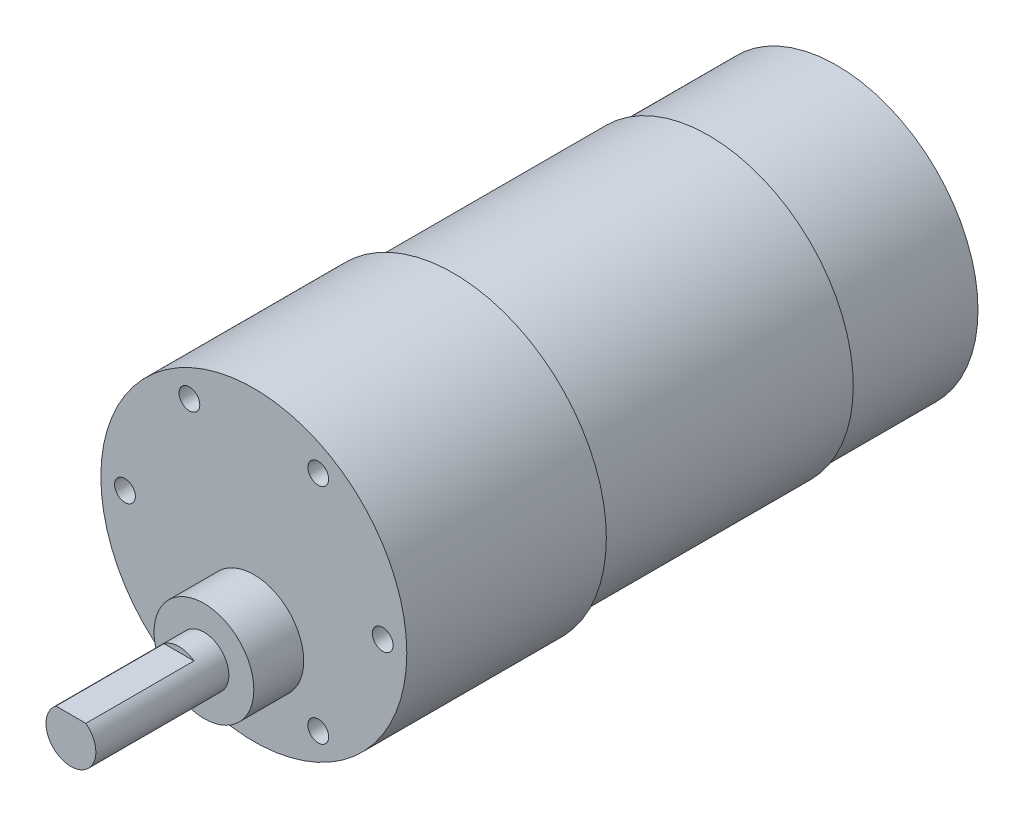
SolidWorks part; units mm, degrees
ref_plane "Front Plane" through (0, 0, 0) normal (0, 0, 1) x (1, 0, 0)
ref_plane "Top Plane" through (0, 0, 0) normal (0, 1, 0) x (1, 0, 0)
ref_plane "Right Plane" through (0, 0, 0) normal (1, 0, 0) x (0, 0, -1)
sketch "Sketch1" plane through (0, 0, 0) normal (0, 0, 1) x (1, 0, 0)
  circle A0 centre (0, 0) radius 18.4
  dimension "D1" = 36.8
extrude "Boss-Extrude1" add sketch "Sketch1" against normal blind 24
sketch "Sketch2" plane through (0, 0, -24) normal (0, 0, -1) x (-1, 0, 0)
  circle A0 centre (0, 0) radius 17.4
  dimension "D1" = 34.8
extrude "Boss-Extrude2" add sketch "Sketch2" along normal blind 30.7
sketch "Sketch3" plane through (0, 0, -54.7) normal (0, 0, -1) x (-1, 0, 0)
  circle A0 centre (0, 0) radius 17
  dimension "D1" = 34
extrude "Boss-Extrude3" add sketch "Sketch3" along normal blind 15.4
sketch "Sketch4" plane through (0, 0, 0) normal (0, 0, 1) x (1, 0, 0)
  circle A0 centre (0, -7) radius 6
  dimension "D1" = 12
  dimension "D2" = 7
extrude "Boss-Extrude4" add sketch "Sketch4" along normal blind 6
sketch "Sketch5" plane through (0, 0, 6) normal (0, 0, 1) x (1, 0, 0)
  line L0 (-1.8, -4.6) -> (1.8, -4.6)
  arc A0 (-1.8, -4.6) -> (1.8, -4.6) centre (0, -7) ccw
  dimension "D1" = 6
  dimension "D2" = 5.4
extrude "Boss-Extrude5" add sketch "Sketch5" along normal blind 16
sketch "Sketch6" plane through (0, 0, 6) normal (0, 0, 1) x (1, 0, 0)
  circle A0 centre (0, -7) radius 3
  arc A1 (-1.8, -4.6) -> (1.8, -4.6) centre (0, -7) ccw construction
extrude "Boss-Extrude6" add sketch "Sketch6" along normal blind 3
sketch "Sketch7" plane through (0, 0, 0) normal (0, 0, 1) x (1, 0, 0)
  line L1 (15.5, 0) -> (7.75, 13.4234)
  line L2 (7.75, 13.4234) -> (-7.75, 13.4234)
  line L3 (-7.75, 13.4234) -> (-15.5, 0)
  line L4 (-15.5, 0) -> (-7.75, -13.4234)
  line L5 (-7.75, -13.4234) -> (7.75, -13.4234)
  line L6 (7.75, -13.4234) -> (15.5, 0)
  circle A0 centre (0, 0) radius 13.4234 construction
  dimension "D1" = 31
  dimension "D2" = 15.5
hole_wizard "M3x0.5 Tapped Hole1" positions "Sketch8" profile "Sketch9" tap size "M3x0.5" standard "ANSI Metric"
sketch "Sketch8" plane through (0, 0, 0) normal (0, 0, 1) x (1, 0, 0)
  point P0 (7.75, 13.4234)
  point P3 (-7.75, 13.4234)
  point P6 (-15.5, 0)
  point P9 (-7.75, -13.4234)
  point P12 (7.75, -13.4234)
  point P15 (15.5, 0)
sketch "Sketch9" plane through (7.75, 13.4234, 0) normal (1, 0, 0) x (0, -1, 0)
  line L0 (0, 0) -> (0, 8.7511)
  line L1 (0, 8.7511) -> (1.25, 8)
  line L2 (1.25, 8) -> (1.25, 0)
  line L5 (1.25, 0) -> (0, 0)
  line L10 (0, 8.7511) -> (-1.25, 8) construction
  line L11 (0, -6.35) -> (0, 107.95) construction
  dimension "Tap Drill Dia." = 2.5
  dimension "Tap Drill Depth" = 8
  dimension "Drill Angle" = 118
cosmetic thread "Hole Thread1"
cosmetic thread "Hole Thread2"
cosmetic thread "Hole Thread3"
cosmetic thread "Hole Thread4"
cosmetic thread "Hole Thread5"
cosmetic thread "Hole Thread6"
